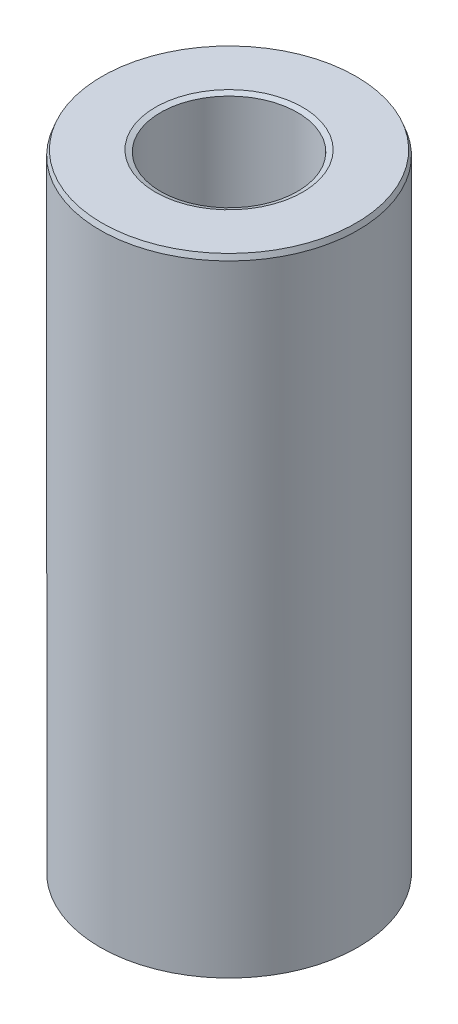
SolidWorks part; units mm, degrees
ref_plane "Front Plane" through (0, 0, 0) normal (0, 0, 1) x (1, 0, 0)
ref_plane "Top Plane" through (0, 0, 0) normal (0, 1, 0) x (1, 0, 0)
ref_plane "Right Plane" through (0, 0, 0) normal (1, 0, 0) x (0, 0, -1)
sketch "Sketch1" plane through (0, 0, 0) normal (0, 1, 0) x (1, 0, 0)
  circle A0 centre (0, 0) radius 45
  dimension "SLEEVE_OD" = 90
extrude "Boss-Extrude1" add sketch "Sketch1" along normal blind 219.1424
sketch "Sketch2" plane through (0, 0, 0) normal (0, 1, 0) x (1, 0, 0)
  circle A0 centre (0, 0) radius 23.8801
  dimension "BORE_D" = 47.7602
extrude "Cut-Extrude1" cut sketch "Sketch2" along normal through all
chamfer "Chamfer1" distance 1.8074 angle 20.546 4 edges at (0, 219.1424, 23.8801) (0, 0, 23.8801) (0, 0, 45) (0, 219.1424, 45) first distance on face at (0, 219.1424, 23.8801) first distance on face at (0, 0, 23.8801) first distance on face at (0, 219.1424, 45)
